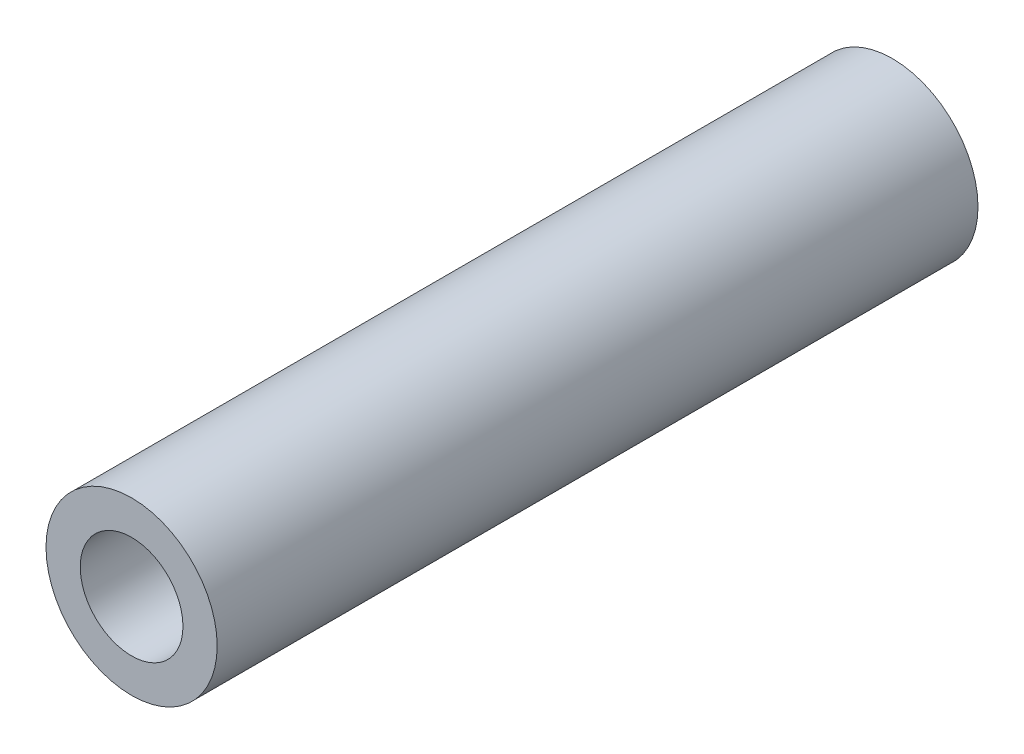
SolidWorks part; units mm, degrees
ref_plane "Front Plane" through (0, 0, 0) normal (0, 0, 1) x (1, 0, 0)
ref_plane "Top Plane" through (0, 0, 0) normal (0, 1, 0) x (1, 0, 0)
ref_plane "Right Plane" through (0, 0, 0) normal (1, 0, 0) x (0, 0, -1)
sketch "Sketch3" plane through (0, 0, 0) normal (0, 0, 1) x (1, 0, 0)
  circle A0 centre (0, 0) radius 1.35 construction
  circle A1 centre (0, 0) radius 2.25 construction
  point P6 (0, -1.35)
  dimension "OD" = 4.5
  dimension "ID" = 2.7
sketch "Sketch1" plane through (0, 0, 0) normal (1, 0, 0) x (0, 0, -1)
  line L0 (-10, -1.35) -> (-10, 1.35) construction
  line L1 (10, -2.25) -> (-10, -2.25) construction
  line L2 (10, -2.25) -> (10, 2.25) construction
  line L3 (10, 2.25) -> (-10, 2.25) construction
  line L4 (-10, -2.25) -> (-10, 2.25) construction
  line L5 (0, 2.25) -> (0, -2.25) construction
  line L6 (10, 0) -> (-10, 0) construction
  point P0 (0, 0)
  point P7 (-10, 0)
  dimension "OD" = 4.5
  dimension "ID" = 2.7
sketch "Sketch2" plane through (0, 0, 0) normal (0, 0, 1) x (1, 0, 0)
  circle A0 centre (0, 0) radius 2.25
  circle A1 centre (0, 0) radius 1.35
extrude "Extrude1" add sketch "Sketch2" along normal up to vertex and the other way up to vertex up to point (0, -2.25, 10) other way up to point (0, 2.25, -10)
equation "\"ID@Sketch1\" = \"ID@Sketch3\""
equation "\"OD@Sketch1\" = \"OD@Sketch3\""
